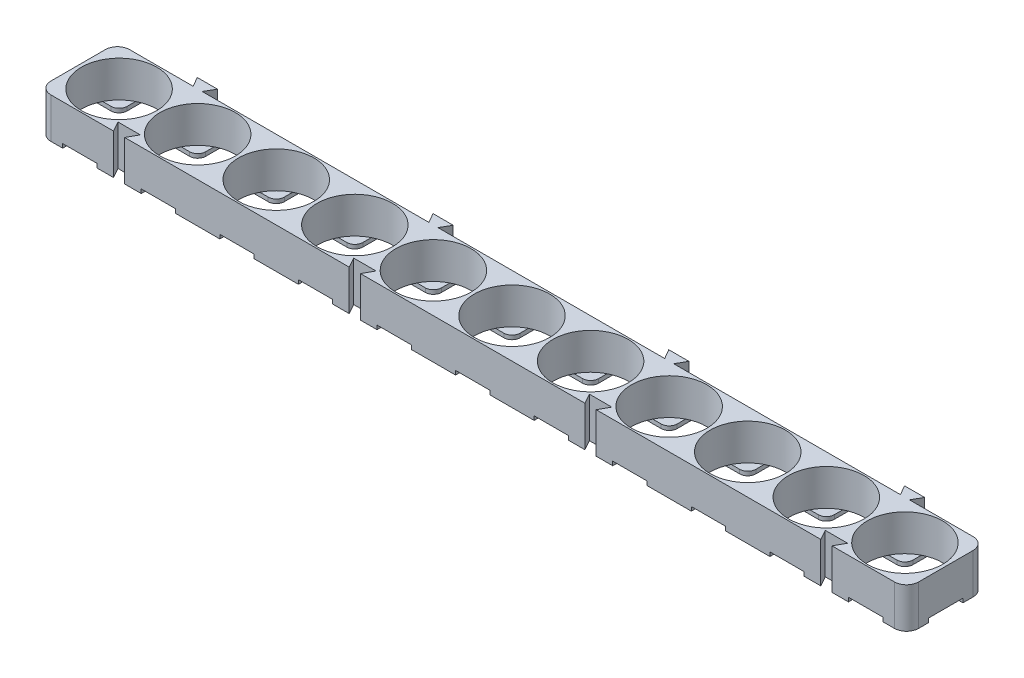
SolidWorks part; units mm, degrees
ref_plane "Front Plane" through (0, 0, 0) normal (0, 0, 1) x (1, 0, 0)
ref_plane "Top Plane" through (0, 0, 0) normal (0, 1, 0) x (1, 0, 0)
ref_plane "Right Plane" through (0, 0, 0) normal (1, 0, 0) x (0, 0, -1)
sketch "Sketch3" plane through (0, 0, 0) normal (0, 1, 0) x (1, 0, 0)
  line L0 (-10.15, 0) -> (9.35, 0) construction
  line L5 (9.35, 9.35) -> (9.35, -9.35) construction
  line L6 (9.35, -9.35) -> (-9.35, -9.35) construction
  line L7 (-9.35, -9.35) -> (-9.35, 9.35) construction
  line L8 (-9.35, 9.35) -> (9.35, 9.35) construction
  line L9 (10.15, -9.35) -> (10.15, 9.35) construction
  line L10 (10.15, 9.35) -> (28.85, 9.35) construction
  line L11 (28.85, 9.35) -> (28.85, -9.35) construction
  line L12 (28.85, -9.35) -> (10.15, -9.35) construction
  line L13 (29.65, -9.35) -> (29.65, 9.35) construction
  line L14 (29.65, 9.35) -> (48.35, 9.35) construction
  line L15 (48.35, 9.35) -> (48.35, -9.35) construction
  line L16 (48.35, -9.35) -> (29.65, -9.35) construction
  line L17 (49.15, -9.35) -> (49.15, 9.35) construction
  line L18 (49.15, 9.35) -> (67.85, 9.35) construction
  line L19 (67.85, 9.35) -> (67.85, -9.35) construction
  line L20 (67.85, -9.35) -> (49.15, -9.35) construction
  line L21 (68.65, -9.35) -> (68.65, 9.35) construction
  line L22 (68.65, 9.35) -> (87.35, 9.35) construction
  line L23 (87.35, 9.35) -> (87.35, -9.35) construction
  line L24 (87.35, -9.35) -> (68.65, -9.35) construction
  line L25 (88.15, -9.35) -> (88.15, 9.35) construction
  line L26 (88.15, 9.35) -> (106.85, 9.35) construction
  line L27 (106.85, 9.35) -> (106.85, -9.35) construction
  line L28 (106.85, -9.35) -> (88.15, -9.35) construction
  line L29 (107.65, -9.35) -> (107.65, 9.35) construction
  line L30 (107.65, 9.35) -> (126.35, 9.35) construction
  line L31 (126.35, 9.35) -> (126.35, -9.35) construction
  line L32 (126.35, -9.35) -> (107.65, -9.35) construction
  line L33 (127.15, -9.35) -> (127.15, 9.35) construction
  line L34 (127.15, 9.35) -> (145.85, 9.35) construction
  line L35 (145.85, 9.35) -> (145.85, -9.35) construction
  line L36 (145.85, -9.35) -> (127.15, -9.35) construction
  line L37 (146.65, -9.35) -> (146.65, 9.35) construction
  line L38 (146.65, 9.35) -> (165.35, 9.35) construction
  line L39 (165.35, 9.35) -> (165.35, -9.35) construction
  line L40 (165.35, -9.35) -> (146.65, -9.35) construction
  line L41 (166.15, -9.35) -> (166.15, 9.35) construction
  line L42 (166.15, 9.35) -> (184.85, 9.35) construction
  line L43 (184.85, 9.35) -> (184.85, -9.35) construction
  line L44 (184.85, -9.35) -> (166.15, -9.35) construction
  line L45 (185.65, -9.35) -> (185.65, 9.35) construction
  line L46 (185.65, 9.35) -> (204.35, 9.35) construction
  line L47 (204.35, 9.35) -> (204.35, -9.35) construction
  line L48 (204.35, -9.35) -> (185.65, -9.35) construction
  line L49 (-10.15, 0) -> (205.15, 0) construction
  line L50 (-10.15, 9.75) -> (205.15, 9.75)
  line L51 (-10.15, 9.75) -> (-10.15, -9.75)
  line L52 (-10.15, -9.75) -> (205.15, -9.75)
  line L53 (205.15, 9.75) -> (205.15, -9.75)
  line L54 (9.35, 9.35) -> (10.15, 9.35) construction
  line L55 (9.75, 28.45) -> (9.75, -9.75) construction
  line L56 (67.85, 9.35) -> (68.65, 9.35) construction
  line L57 (68.25, 9.35) -> (68.25, 13.7208) construction
  line L58 (12.25, 12.15) -> (7.25, 12.15)
  line L59 (7.25, 12.15) -> (8.6356, 9.75)
  line L60 (8.6356, 9.75) -> (10.8644, 9.75)
  line L61 (12.25, 12.15) -> (10.8644, 9.75)
  line L62 (12.525, -7.25) -> (6.975, -7.25)
  line L63 (6.975, -7.25) -> (8.3608, -9.75)
  line L64 (8.3608, -9.75) -> (11.1392, -9.75)
  line L65 (12.525, -7.25) -> (11.1392, -9.75)
  line L66 (67.1356, 9.75) -> (69.3644, 9.75)
  line L67 (70.75, 12.15) -> (69.3644, 9.75)
  line L68 (70.75, 12.15) -> (65.75, 12.15)
  line L69 (65.75, 12.15) -> (67.1356, 9.75)
  line L70 (66.8608, -9.75) -> (69.6392, -9.75)
  line L71 (71.025, -7.25) -> (69.6392, -9.75)
  line L72 (71.025, -7.25) -> (65.475, -7.25)
  line L73 (65.475, -7.25) -> (66.8608, -9.75)
  line L74 (125.6356, 9.75) -> (127.8644, 9.75)
  line L75 (129.25, 12.15) -> (127.8644, 9.75)
  line L76 (129.25, 12.15) -> (124.25, 12.15)
  line L77 (124.25, 12.15) -> (125.6356, 9.75)
  line L78 (125.3608, -9.75) -> (128.1392, -9.75)
  line L79 (129.525, -7.25) -> (128.1392, -9.75)
  line L80 (129.525, -7.25) -> (123.975, -7.25)
  line L81 (123.975, -7.25) -> (125.3608, -9.75)
  line L82 (184.1356, 9.75) -> (186.3644, 9.75)
  line L83 (187.75, 12.15) -> (186.3644, 9.75)
  line L84 (187.75, 12.15) -> (182.75, 12.15)
  line L85 (182.75, 12.15) -> (184.1356, 9.75)
  line L86 (183.8608, -9.75) -> (186.6392, -9.75)
  line L87 (188.025, -7.25) -> (186.6392, -9.75)
  line L88 (188.025, -7.25) -> (182.475, -7.25)
  line L89 (182.475, -7.25) -> (183.8608, -9.75)
  line L90 (68.25, 12.15) -> (68.25, 9.75) construction
  circle A0 centre (0, 0) radius 9.35
  circle A1 centre (19.5, 0) radius 9.35
  circle A2 centre (39, 0) radius 9.35
  circle A3 centre (58.5, 0) radius 9.35
  circle A4 centre (78, 0) radius 9.35
  circle A5 centre (97.5, 0) radius 9.35
  circle A6 centre (117, 0) radius 9.35
  circle A7 centre (136.5, 0) radius 9.35
  circle A8 centre (156, 0) radius 9.35
  circle A9 centre (175.5, 0) radius 9.35
  circle A10 centre (195, 0) radius 9.35
  point P10 (-0.4, 0)
  point P13 (-9.35, 0)
  point P16 (0, 9.35)
  point P84 (9.75, 9.35)
  point P88 (9.75, 9.75)
  point P89 (9.75, 12.15)
  point P94 (9.75, -7.25)
  dimension "D1" = 18.7
  dimension "D2" = 11
  dimension "D3" = 0.8
  dimension "D4" = 0.4
  dimension "D5" = 0.8
  dimension "D6" = 0.8
  dimension "D7" = 215.3
  dimension "D8" = 19.5
  dimension "D9" = 5
  dimension "D10" = 60
  dimension "D11" = 2.4
  dimension "D12" = 5.55
  dimension "D13" = 61
  dimension "D14" = 2.5
  dimension "D16" = 19.5
  dimension "D15" = 4
extrude "Boss-Extrude3" add sketch "Sketch3" along normal blind 10 contours L89 L88 L87 L52 L53 L50 L51 L63 L62 L65 L73 L72 L71 L81 L80 L79 A10 A9 A8 A7 A6 A5 A4 A3 A2 A1 A0 | L61 L58 L59 L50 | L68 L69 L50 L67 | L76 L77 L50 L75 | L84 L85 L50 L83 region at (-0.7572, 0, -9.5338) region at (9.75, 0, -11.1033) region at (68.25, 0, -11.1033) region at (126.75, 0, -11.1033) region at (185.25, 0, -11.1033)
extrude "Boss-Extrude6" add sketch "Sketch3<4>" along normal blind 1 contours A0 | A1 | A2 | A3 | A4 | A5 | A6 | A7 | A8 | A9 | A10 region at (0, 0, 0) region at (19.5, 0, 0) region at (39, 0, 0) region at (58.5, 0, 0) region at (78, 0, 0) region at (97.5, 0, 0) region at (117, 0, 0) region at (136.5, 0, 0) region at (156, 0, 0) region at (175.5, 0, 0) region at (195, 0, 0)
sketch "Sketch3<4>" plane through (0, 0, 0) normal (0, 1, 0) x (1, 0, 0) same geometry as "Sketch3"
sketch "Sketch8" plane through (0, 1, 0) normal (0, 1, 0) x (1, 0, 0)
  line L0 (-9.35, 0) -> (9.35, 0) construction
  line L1 (0, -9.35) -> (0, 9.35) construction
  line L2 (19.5, -9.35) -> (19.5, 9.35) construction
  line L3 (205.15, 9.75) -> (205.15, -9.75) construction
  line L4 (-10.15, -4.25) -> (205.15, -4.25)
  line L5 (-10.15, -4.25) -> (-10.15, 4.25)
  line L6 (-10.15, 4.25) -> (205.15, 4.25)
  line L7 (205.15, -4.25) -> (205.15, 4.25)
  line L8 (-10.15, -4.25) -> (205.15, 4.25) construction
  line L9 (-10.15, 4.25) -> (205.15, -4.25) construction
  line L10 (-10.15, 9.75) -> (8.6356, 9.75) construction
  line L11 (-4.25, -9.75) -> (4.25, -9.75)
  line L12 (-4.25, -9.75) -> (-4.25, 9.75)
  line L13 (-4.25, 9.75) -> (4.25, 9.75)
  line L14 (4.25, -9.75) -> (4.25, 9.75)
  line L15 (-4.25, -9.75) -> (4.25, 9.75) construction
  line L16 (-4.25, 9.75) -> (4.25, -9.75) construction
  line L17 (15.25, -9.75) -> (15.25, 9.75)
  line L18 (15.25, -9.75) -> (23.75, -9.75)
  line L19 (23.75, -9.75) -> (23.75, 9.75)
  line L20 (15.25, 9.75) -> (23.75, 9.75)
  line L21 (34.75, -9.75) -> (34.75, 9.75)
  line L22 (34.75, -9.75) -> (43.25, -9.75)
  line L23 (43.25, -9.75) -> (43.25, 9.75)
  line L24 (34.75, 9.75) -> (43.25, 9.75)
  line L25 (54.25, -9.75) -> (54.25, 9.75)
  line L26 (54.25, -9.75) -> (62.75, -9.75)
  line L27 (62.75, -9.75) -> (62.75, 9.75)
  line L28 (54.25, 9.75) -> (62.75, 9.75)
  line L29 (73.75, -9.75) -> (73.75, 9.75)
  line L30 (73.75, -9.75) -> (82.25, -9.75)
  line L31 (82.25, -9.75) -> (82.25, 9.75)
  line L32 (73.75, 9.75) -> (82.25, 9.75)
  line L33 (93.25, -9.75) -> (93.25, 9.75)
  line L34 (93.25, -9.75) -> (101.75, -9.75)
  line L35 (101.75, -9.75) -> (101.75, 9.75)
  line L36 (93.25, 9.75) -> (101.75, 9.75)
  line L37 (112.75, -9.75) -> (112.75, 9.75)
  line L38 (112.75, -9.75) -> (121.25, -9.75)
  line L39 (121.25, -9.75) -> (121.25, 9.75)
  line L40 (112.75, 9.75) -> (121.25, 9.75)
  line L41 (132.25, -9.75) -> (132.25, 9.75)
  line L42 (132.25, -9.75) -> (140.75, -9.75)
  line L43 (140.75, -9.75) -> (140.75, 9.75)
  line L44 (132.25, 9.75) -> (140.75, 9.75)
  line L45 (151.75, -9.75) -> (151.75, 9.75)
  line L46 (151.75, -9.75) -> (160.25, -9.75)
  line L47 (160.25, -9.75) -> (160.25, 9.75)
  line L48 (151.75, 9.75) -> (160.25, 9.75)
  line L49 (171.25, -9.75) -> (171.25, 9.75)
  line L50 (171.25, -9.75) -> (179.75, -9.75)
  line L51 (179.75, -9.75) -> (179.75, 9.75)
  line L52 (171.25, 9.75) -> (179.75, 9.75)
  line L53 (190.75, -9.75) -> (190.75, 9.75)
  line L54 (190.75, -9.75) -> (199.25, -9.75)
  line L55 (199.25, -9.75) -> (199.25, 9.75)
  line L56 (190.75, 9.75) -> (199.25, 9.75)
  line L57 (15.25, 9.75) -> (23.75, -9.75) construction
  circle A2 centre (0, 0) radius 9.35
  circle A3 centre (0, 0) radius 9.35 construction
  circle A5 centre (19.5, 0) radius 9.35
  circle A6 centre (19.5, 0) radius 9.35 construction
  point P3 (0, 0)
  point P12 (0, 0)
  point P14 (19.5, 0)
  point P15 (97.5, 0)
  dimension "D3" = 19.5
  dimension "D4" = 8.5
  dimension "D5" = 11
  dimension "D1" = 0
  dimension "D2" = 0
extrude "Cut-Extrude4" cut sketch "Sketch8" against normal through all contours L6 L7 L4 L5 | L12 L13 L14 L11 | L17 L20 L19 L18 | L21 L24 L23 L22 | L25 L28 L27 L26 | L29 L32 L31 L30 | L33 L36 L35 L34 | L37 L40 L39 L38 | L41 L44 L43 L42 | L45 L48 L47 L46 | L49 L52 L51 L50 | L53 L56 L55 L54
fillet "Fillet3" radius 2 44 edges at (4.25, 0.5, -4.25) (-4.25, 0.5, -4.25) (4.25, 0.5, 4.25) (-4.25, 0.5, 4.25) (190.75, 0.5, -4.25) (190.75, 0.5, 4.25) (171.25, 0.5, -4.25) (171.25, 0.5, 4.25) (151.75, 0.5, 4.25) (151.75, 0.5, -4.25) (132.25, 0.5, -4.25) (132.25, 0.5, 4.25) (112.75, 0.5, -4.25) (93.25, 0.5, 4.25) (93.25, 0.5, -4.25) (73.75, 0.5, 4.25) (73.75, 0.5, -4.25) (54.25, 0.5, -4.25) (54.25, 0.5, 4.25) (34.75, 0.5, 4.25) (62.75, 0.5, -4.25) (62.75, 0.5, 4.25) (82.25, 0.5, -4.25) (82.25, 0.5, 4.25) (101.75, 0.5, -4.25) (101.75, 0.5, 4.25) (121.25, 0.5, -4.25) (121.25, 0.5, 4.25) (140.75, 0.5, 4.25) (140.75, 0.5, -4.25) (160.25, 0.5, -4.25) (160.25, 0.5, 4.25) (179.75, 0.5, 4.25) (179.75, 0.5, -4.25) (199.25, 0.5, -4.25) (199.25, 0.5, 4.25) (43.25, 0.5, 4.25) (43.25, 0.5, -4.25) (23.75, 0.5, -4.25) (23.75, 0.5, 4.25) (15.25, 0.5, 4.25) (15.25, 0.5, -4.25) (34.75, 0.5, -4.25) (112.75, 0.5, 4.25)
fillet "Fillet4" radius 3 4 edges at (205.15, 5, 9.75) (205.15, 5, -9.75) (-10.15, 5, 9.75) (-10.15, 5, -9.75)
equation "\"`\"=10"
